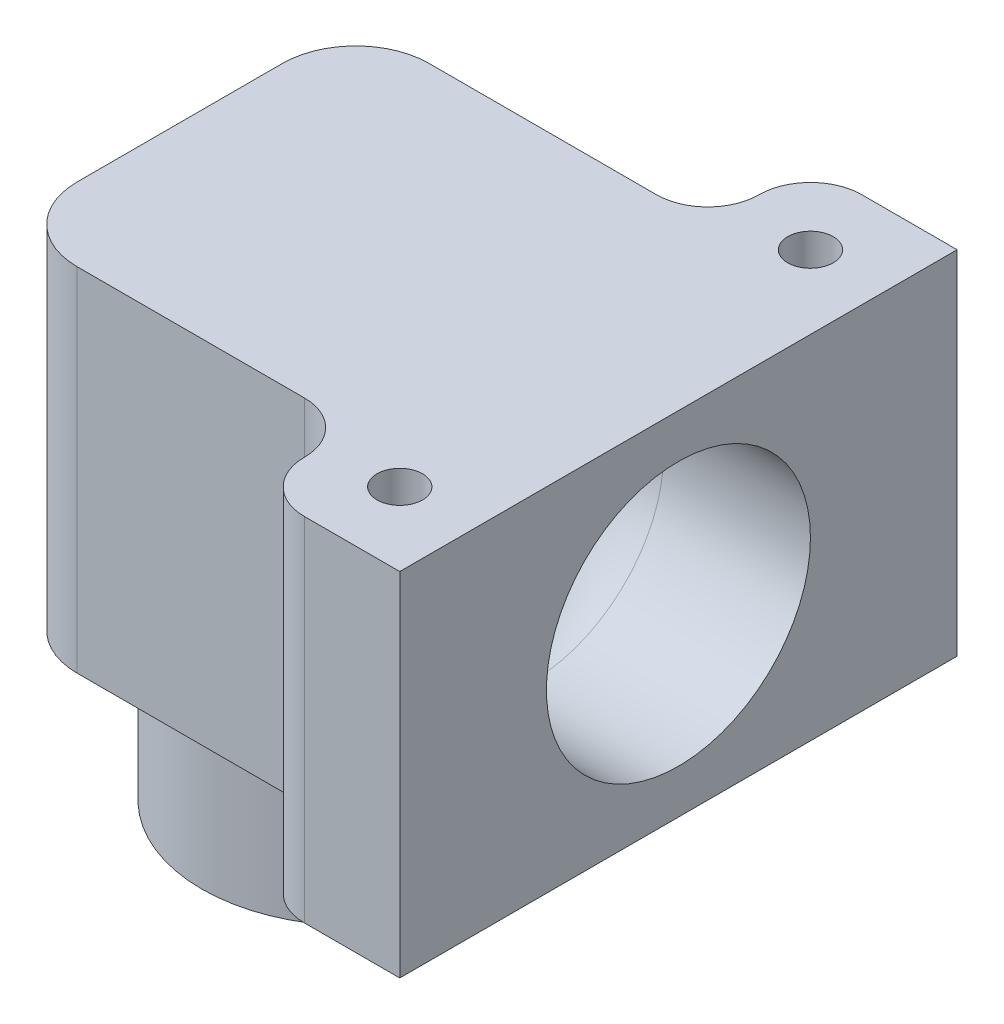
SolidWorks part; units mm, degrees
ref_plane "前视基准面" through (0, 0, 0) normal (0, 0, 1) x (1, 0, 0)
ref_plane "上视基准面" through (0, 0, 0) normal (0, 1, 0) x (1, 0, 0)
ref_plane "右视基准面" through (0, 0, 0) normal (1, 0, 0) x (0, 0, -1)
sketch "草图1" plane through (0, 0, 0) normal (0, 1, 0) x (1, 0, 0)
  line L0 (-5, 0) -> (0, 0) construction
  line L1 (-10, -19) -> (0, -19)
  line L2 (-10, -19) -> (-10, 19)
  line L3 (-10, 19) -> (0, 19)
  line L4 (0, -19) -> (0, 19)
  line L5 (-10, -19) -> (0, 19) construction
  line L6 (-10, 19) -> (0, -19) construction
  line L7 (-5, 14) -> (-5, -14) construction
  circle A0 centre (-5, 14) radius 1.55
  circle A1 centre (-5, -14) radius 1.55
  point P0 (-5, 0)
  point P10 (-5, 0)
  dimension "D3" = 3.1
  dimension "D1" = 10
  dimension "D2" = 38
  dimension "D4" = 28
extrude "凸台-拉伸1" add sketch "草图1" along normal blind 12 and the other way blind 12
sketch "草图2" plane through (-10, 0, 0) normal (-1, 0, 0) x (0, 0, 1)
  line L0 (-19, 12) -> (19, 12) construction
  line L12 (12, -12) -> (-12, -12)
  line L13 (12, -12) -> (12, 12)
  line L14 (12, 12) -> (-12, 12)
  line L15 (-12, -12) -> (-12, 12)
  line L16 (12, -12) -> (-12, 12) construction
  line L17 (12, 12) -> (-12, -12) construction
  line L19 (-19, -12) -> (19, -12) construction
  point P0 (0, 0)
  point P5 (0, 0)
  point P6 (0, 0)
  point P7 (0, 0)
  point P9 (0, 0)
  point P12 (0, 0)
  point P13 (12, 11.3296)
  point P14 (0, 0)
  point P15 (0, 0)
  point P19 (0, 0)
  point P20 (0, 0)
  point P21 (0, 0)
  point P22 (0, 0)
  dimension "D1" = 24
extrude "凸台-拉伸4" add sketch "草图2" along normal blind 24
sketch "草图3" plane through (0, 0, 0) normal (0, 0, 1) x (1, 0, 0)
  line L0 (-10, -12) -> (-10, 12) construction
  line L1 (-10, 11) -> (0, 11)
  line L2 (0, -12) -> (0, 12) construction
  arc A0 (-10, 11) -> (-32.9135, -13.9925) centre (-10, -12) ccw
  dimension "D1" = 23
sketch "草图4" plane through (0, 0, 0) normal (1, 0, 0) x (0, 0, -1)
  circle A0 centre (0, 0) radius 9
  dimension "D1" = 18
sweep "切除-扫描1" cut profiles "草图4" path "草图3"
sketch "草图5" plane through (0, -12, 0) normal (0, -1, 0) x (1, 0, 0)
  line L0 (-22, 0) -> (-22, -9) construction
  line L1 (-22, 0) -> (0, 0) construction
  circle A0 centre (-22, 0) radius 10.5
  spline S1 degree 3 poles (-22, -9) (-4, -9) (-4, 9) (-22, 9) (-40, 9) (-40, -9) (-22, -9) (-4, -9) (-4, 9) knots -0.5 0 0 0 0.5 0.5 0.5 1 1 1 1.5 1.5 1.5 weights 1 0.333333 0.333333 1 0.333333 0.333333 1 0.333333 0.333333 only from (-22, -9) to (-22, -9) construction
  spline S2 degree 3 poles (-22, -9) (-4, -9) (-4, 9) (-22, 9) (-40, 9) (-40, -9) (-22, -9) (-4, -9) (-4, 9) knots -0.5 0 0 0 0.5 0.5 0.5 1 1 1 1.5 1.5 1.5 weights 1 0.333333 0.333333 1 0.333333 0.333333 1 0.333333 0.333333 only from (-22, -9) to (-22, -9)
  dimension "D1" = 21
extrude "凸台-拉伸3" add sketch "草图5" along normal blind 10
fillet "圆角1" radius 5 2 edges at (-34, 0, -12) (-34, 0, 12)
fillet "圆角2" radius 3.5 4 edges at (-10, 0, -19) (-10, 0, -12) (-10, 0, 19) (-10, 0, 12)
